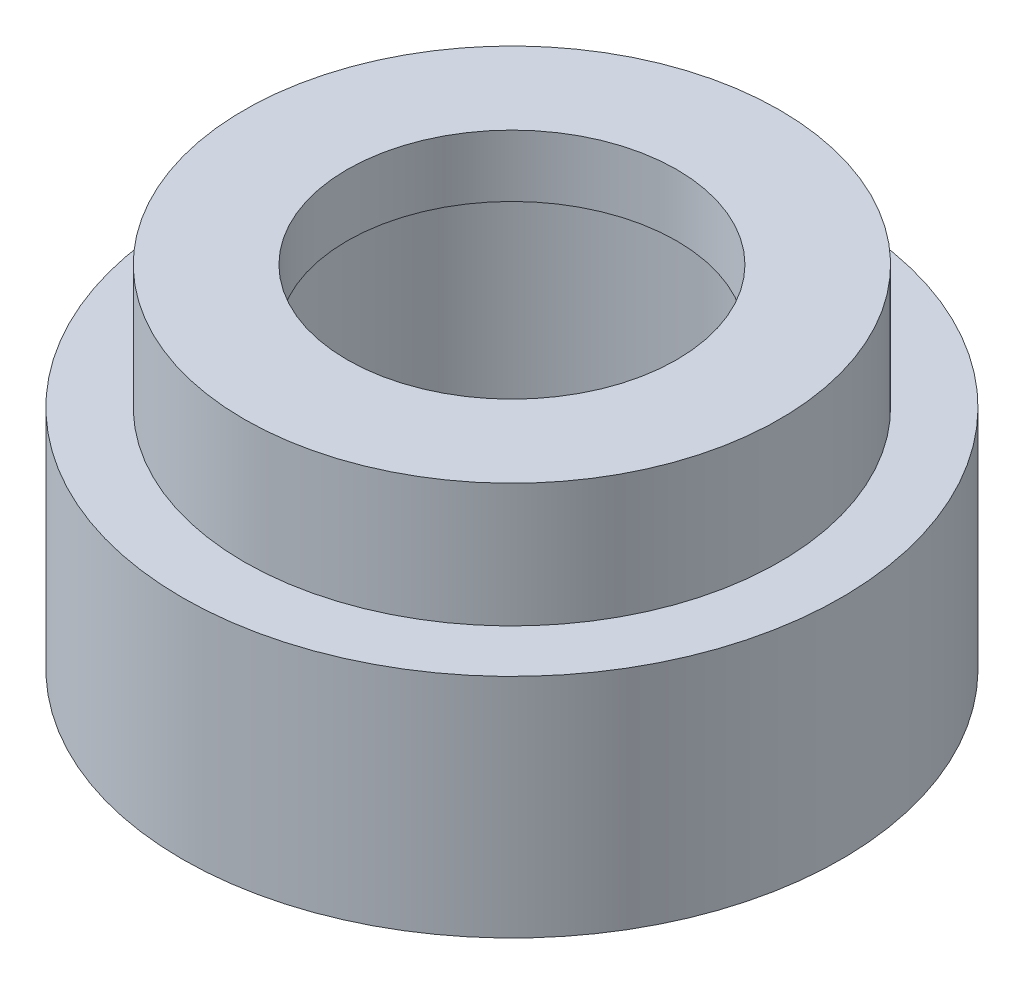
SolidWorks part; units mm, degrees
ref_plane "Front Plane" through (0, 0, 0) normal (0, 0, 1) x (1, 0, 0)
ref_plane "Top Plane" through (0, 0, 0) normal (0, 1, 0) x (1, 0, 0)
ref_plane "Right Plane" through (0, 0, 0) normal (1, 0, 0) x (0, 0, -1)
sketch "Sketch1" plane through (0, 0, 0) normal (0, 1, 0) x (1, 0, 0)
  circle A0 centre (0, 0) radius 8
  dimension "D1" = 16
extrude "Boss-Extrude1" add sketch "Sketch1" along normal blind 5.5
sketch "Sketch2" plane through (0, 5.5, 0) normal (0, 1, 0) x (1, 0, 0)
  circle A0 centre (0, 0) radius 6.5
  dimension "D1" = 13
extrude "Boss-Extrude2" add sketch "Sketch2" along normal blind 3
sketch "Sketch3" plane through (0, 0, 0) normal (0, -1, 0) x (1, 0, 0)
  circle A0 centre (0, 0) radius 5.1
  dimension "D1" = 10.2
extrude "Cut-Extrude1" cut sketch "Sketch3" against normal blind 7
sketch "Sketch4" plane through (0, 8.5, 0) normal (0, 1, 0) x (1, 0, 0)
  circle A0 centre (0, 0) radius 4
  dimension "D1" = 8
extrude "Cut-Extrude2" cut sketch "Sketch4" against normal blind 7
